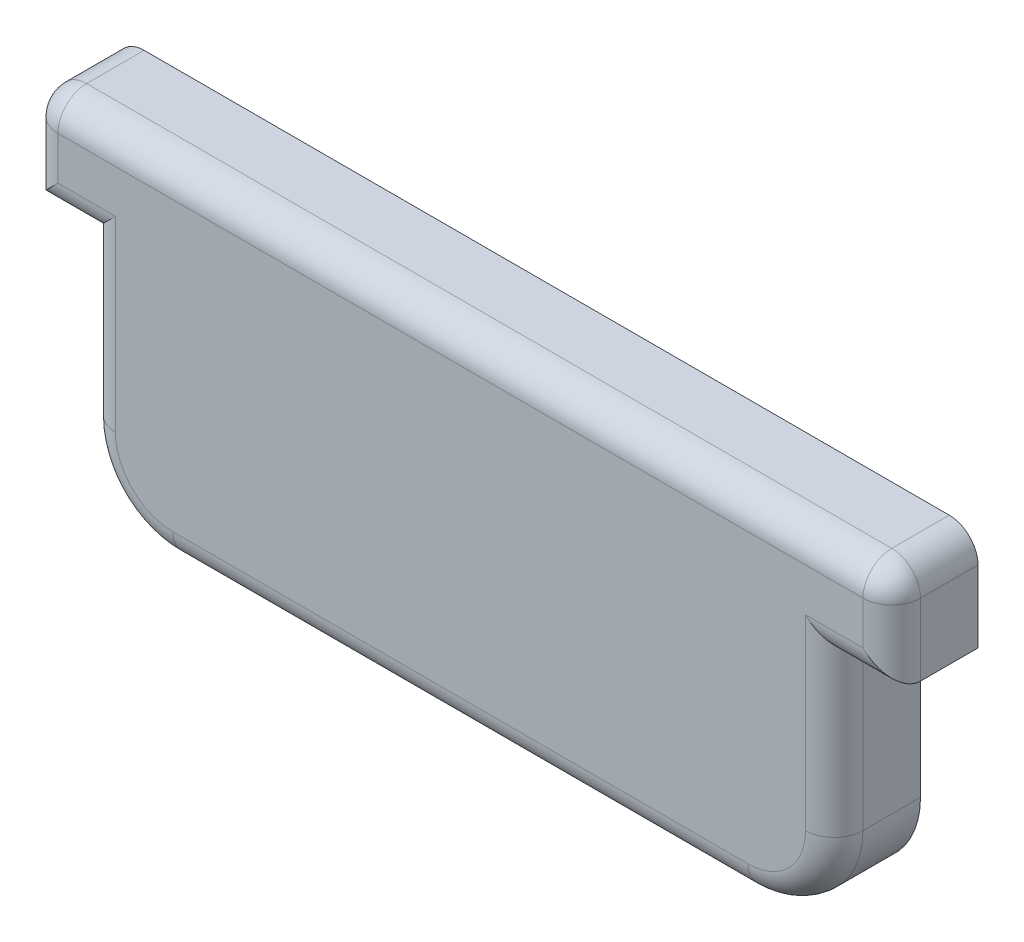
SolidWorks part; units mm, degrees
ref_plane "Front Plane" through (0, 0, 0) normal (0, 0, 1) x (1, 0, 0)
ref_plane "Top Plane" through (0, 0, 0) normal (0, 1, 0) x (1, 0, 0)
ref_plane "Right Plane" through (0, 0, 0) normal (1, 0, 0) x (0, 0, -1)
sketch "Sketch1" plane through (0, 0, 0) normal (0, 0, 1) x (1, 0, 0)
  line L0 (40, 52.5) -> (40, 80) construction
  line L1 (-70, 42.5) -> (30, 42.5) construction
  line L2 (-80, 80) -> (-80, 52.5) construction
  line L3 (40, 52.5) -> (40, 80)
  line L4 (-70, 42.5) -> (30, 42.5)
  line L5 (-80, 80) -> (-80, 52.5)
  line L6 (-85, 80) -> (-85, 52.5)
  line L7 (-70, 37.5) -> (30, 37.5)
  line L8 (45, 52.5) -> (45, 80)
  line L9 (45, 80) -> (40, 80)
  line L10 (-85, 80) -> (-80, 80)
  arc A0 (30, 42.5) -> (40, 52.5) centre (30, 52.5) ccw construction
  arc A1 (-80, 52.5) -> (-70, 42.5) centre (-70, 52.5) ccw construction
  arc A2 (30, 42.5) -> (40, 52.5) centre (30, 52.5) ccw
  arc A3 (-80, 52.5) -> (-70, 42.5) centre (-70, 52.5) ccw
  arc A4 (-85, 52.5) -> (-70, 37.5) centre (-70, 52.5) ccw
  arc A5 (30, 37.5) -> (45, 52.5) centre (30, 52.5) ccw
  dimension "D1" = 5
extrude "Boss-Extrude2" add sketch "Sketch1" along normal blind 10
sketch "Sketch2" plane through (0, 0, 10) normal (0, 0, 1) x (1, 0, 0)
  line L0 (45, 52.5) -> (45, 80) construction
  line L1 (-85, 80) -> (-85, 52.5) construction
  line L2 (-70, 37.5) -> (30, 37.5) construction
  line L3 (45, 52.5) -> (45, 80)
  line L4 (-85, 80) -> (-85, 52.5)
  line L5 (-70, 37.5) -> (30, 37.5)
  line L6 (45, 80) -> (-85, 80)
  arc A0 (30, 37.5) -> (45, 52.5) centre (30, 52.5) ccw construction
  arc A1 (-85, 52.5) -> (-70, 37.5) centre (-70, 52.5) ccw construction
  arc A2 (30, 37.5) -> (45, 52.5) centre (30, 52.5) ccw
  arc A3 (-85, 52.5) -> (-70, 37.5) centre (-70, 52.5) ccw
extrude "Boss-Extrude3" add sketch "Sketch2" along normal blind 5
fillet "Fillet1" radius 10 5 edges at (-77.0711, 45.4289, 10) (-20, 42.5, 10) (37.0711, 45.4289, 10)
sketch "Sketch3" plane through (0, 80, 0) normal (0, 1, 0) x (1, 0, 0)
  line L0 (-80, 0) -> (-85, 0) construction
  line L1 (55, -15) -> (-95, -15)
  line L2 (55, -15) -> (55, 0)
  line L3 (55, 0) -> (-95, 0)
  line L4 (-95, -15) -> (-95, 0)
  line L5 (55, -15) -> (-95, 0) construction
  line L6 (55, 0) -> (-95, -15) construction
  line L7 (-20, -7.5) -> (-20, -15) construction
  line L8 (45, -15) -> (-85, -15) construction
  point P0 (-20, -7.5)
  dimension "D1" = 150
extrude "Boss-Extrude4" add sketch "Sketch3" along normal blind 17.5 contours L3 L4 L1 L2
sketch "Sketch5" plane through (0, 0, 0) normal (0, 0, -1) x (-1, 0, 0)
  line L0 (-55, 80) -> (-45, 80) construction
  line L1 (-51, 80) -> (0, 80)
  line L2 (-51, 80) -> (-51, 94.2307)
  line L3 (-51, 94.2307) -> (0, 94.2307)
  line L4 (0, 80) -> (0, 94.2307)
  line L5 (20, 97.5) -> (20, 80) construction
  line L6 (-55, 97.5) -> (95, 97.5) construction
  line L7 (-40, 80) -> (80, 80) construction
  line L8 (-30, 80) -> (70, 80) construction
  line L9 (40, 80) -> (91, 80)
  line L10 (40, 80) -> (40, 94.2307)
  line L11 (40, 94.2307) -> (91, 94.2307)
  line L12 (91, 80) -> (91, 94.2307)
  dimension "D1" = 20
  dimension "D2" = 51
  dimension "D3" = 20
  dimension "D4" = 51
extrude "Cut-Extrude1" cut sketch "Sketch5" against normal blind 3
fillet "Fillet2" radius 5 12 edges at (-20, 37.5, 15) (-80.6066, 41.8934, 15) (-95, 88.75, 15) (-20, 97.5, 15) (55, 88.75, 15) (40.6066, 41.8934, 15) (-95, 97.5, 7.5) (55, 97.5, 7.5)
